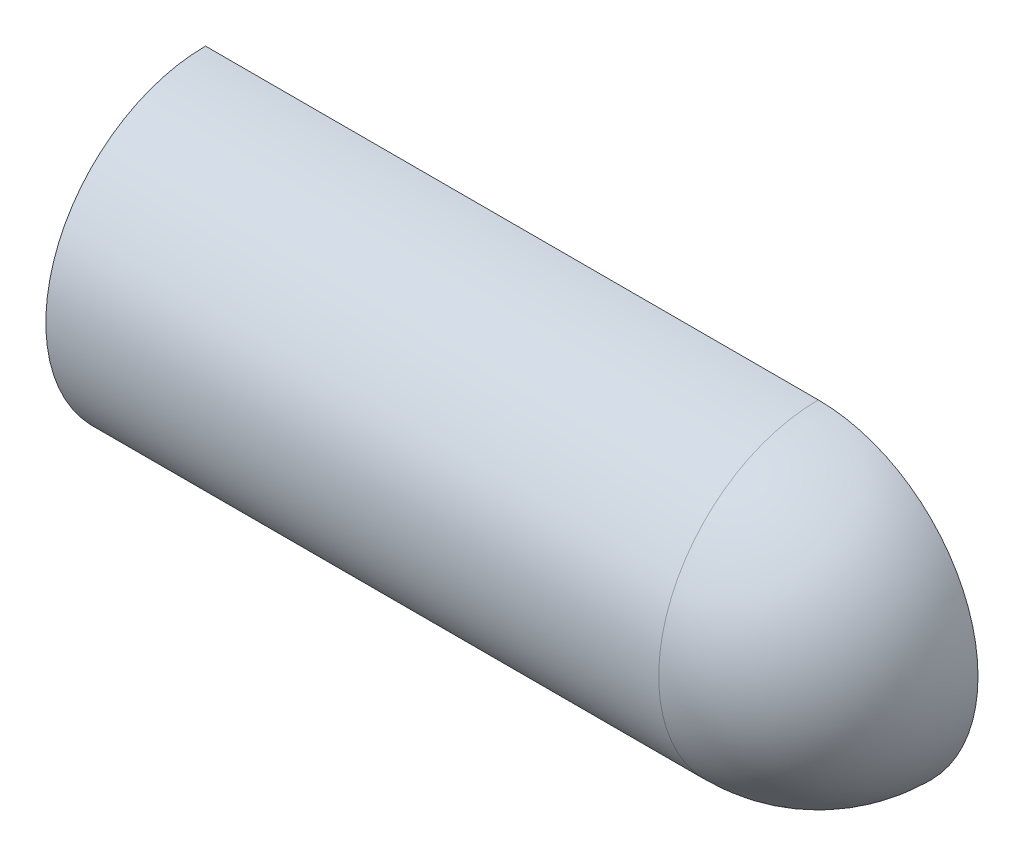
SolidWorks part; units mm, degrees
ref_plane "Front Plane" through (0, 0, 0) normal (0, 0, 1) x (1, 0, 0)
ref_plane "Top Plane" through (0, 0, 0) normal (0, 1, 0) x (1, 0, 0)
ref_plane "Right Plane" through (0, 0, 0) normal (1, 0, 0) x (0, 0, -1)
sketch "Sketch2" plane through (0, 0, 0) normal (0, 0, 1) x (1, 0, 0)
  line L0 (26, 0) -> (31, 0)
  line L2 (-119, 31) -> (0, 31)
  line L3 (-119, 31) -> (-119, 26)
  line L4 (0, 26) -> (-119, 26)
  arc A0 (-2.701, -30.8821) -> (2.701, 30.8821) centre (0, 0) ccw construction
  circle A1 centre (0, 0) radius 31 construction
  arc A3 (31, 0) -> (0, 31) centre (0, 0) ccw
  arc A4 (26, 0) -> (0, 26) centre (0, 0) ccw
revolve "Revolve1" add sketch "Sketch2" angle 180 about L0
